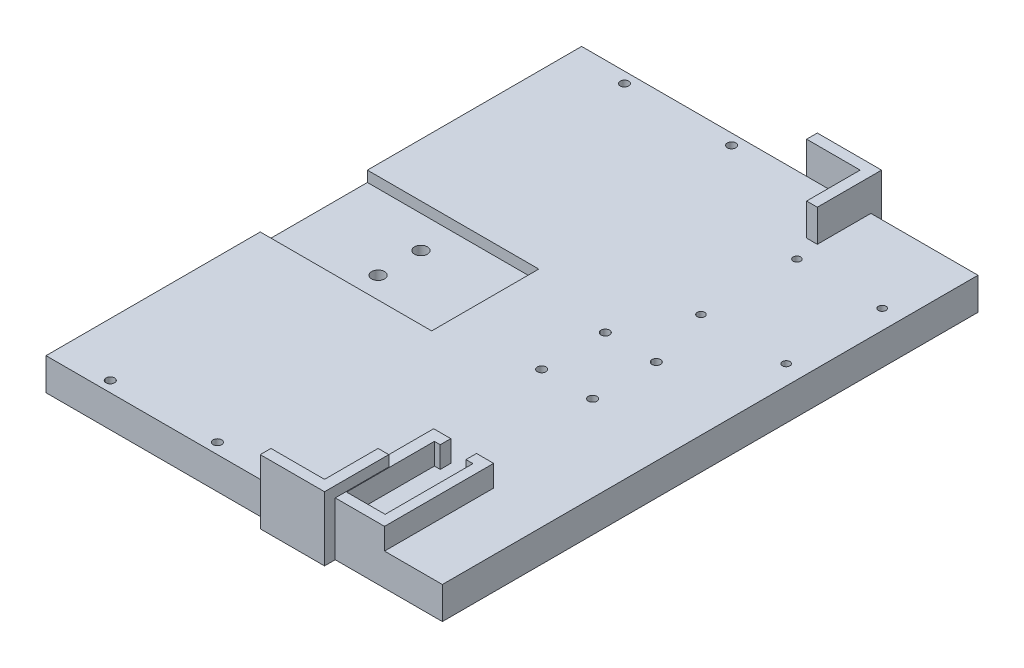
SolidWorks part; units mm, degrees
ref_plane "Ebene vorne" through (0, 0, 0) normal (0, 0, 1) x (1, 0, 0)
ref_plane "Ebene oben" through (0, 0, 0) normal (0, 1, 0) x (1, 0, 0)
ref_plane "Ebene rechts" through (0, 0, 0) normal (1, 0, 0) x (0, 0, -1)
sketch "Skizze1" plane through (0, 0, 0) normal (0, 1, 0) x (1, 0, 0)
  line L5 (-175, -125) -> (175, 125) construction
  line L6 (-175, 125) -> (175, -125) construction
  line L11 (-105, 125) -> (145, 125)
  line L12 (-105, -125) -> (-105, -65)
  line L13 (-105, 125) -> (-105, 65)
  line L14 (-105, -65) -> (-175, -65)
  line L15 (-105, 65) -> (-175, 65)
  line L17 (-105, -125) -> (145, -125)
  line L19 (185, 20) -> (145, 125)
  line L21 (175, 0) -> (175, 20)
  line L22 (175, 20) -> (185, 20)
  line L23 (185, 0) -> (185, 20)
  line L25 (185, 0) -> (185, -20)
  line L26 (185, -20) -> (175, -20)
  line L27 (175, 0) -> (175, -20)
  line L28 (185, -20) -> (145, -125)
  line L29 (-175, 65) -> (-175, -65)
  point P0 (0, 0)
  dimension "D1" = 350
  dimension "D2" = 250
  dimension "D3" = 60
  dimension "D4" = 250
  dimension "D5" = 40
  dimension "D6" = 130
  dimension "D7" = 70
  dimension "D8" = 20
  dimension "D9" = 10
extrude "Aufsatz-Linear austragen1" add sketch "Skizze1" along normal blind 15 contours L15 L29 L14 L12 L17 L28 L26 L27 L21 L22 L19 L11 L13 | L21 L27 L26 L25 L23 L22 region at (10.8182, 0, 0) region at (180, 0, 0)
sketch "Skizze2" plane through (0, 15, 0) normal (0, 1, 0) x (1, 0, 0)
  line L0 (-175, 65) -> (-175, -65) construction
  line L9 (-175, 62) -> (-110, 62)
  line L10 (-175, 62) -> (-175, 42)
  line L11 (-175, 42) -> (-110, 42)
  line L12 (-110, 62) -> (-110, 42)
  line L13 (-105, 65) -> (-175, 65) construction
  line L14 (-175, -42) -> (-110, -42)
  line L15 (-175, -42) -> (-175, -62)
  line L16 (-175, -62) -> (-110, -62)
  line L17 (-110, -42) -> (-110, -62)
  line L18 (-105, -65) -> (-175, -65) construction
  line L19 (-105, 125) -> (145, 125) construction
  line L24 (-125, -62) -> (-120, -62)
  line L25 (-125, -62) -> (-125, -65)
  line L26 (-125, -65) -> (-120, -65)
  line L27 (-120, -62) -> (-120, -65)
  line L28 (-125, -42) -> (-120, -42)
  line L29 (-125, -42) -> (-125, -38)
  line L30 (-125, -38) -> (-120, -38)
  line L31 (-120, -42) -> (-120, -38)
  line L32 (-125, 42) -> (-120, 42)
  line L33 (-125, 42) -> (-125, 38)
  line L34 (-125, 38) -> (-120, 38)
  line L35 (-120, 42) -> (-120, 38)
  line L36 (-125, 65) -> (-120, 65)
  line L37 (-125, 65) -> (-125, 62)
  line L38 (-125, 62) -> (-120, 62)
  line L39 (-120, 65) -> (-120, 62)
  line L40 (-105, -125) -> (145, -125)
  line L41 (-105, -125) -> (-105, 125)
  line L42 (-105, 125) -> (145, 125)
  line L43 (145, -125) -> (145, 125)
  line L46 (145, -125) -> (195, -125)
  line L47 (145, -125) -> (145, 125)
  line L48 (145, 125) -> (195, 125)
  line L49 (195, -125) -> (195, 125)
  line M8 (-105, 65) -> (-175, 65)
  dimension "D1" = 65
  dimension "D2" = 65
  dimension "D3" = 20
  dimension "D4" = 20
  dimension "D5" = 3
  dimension "D6" = 3
  dimension "D7" = 5
  dimension "D8" = 50
  dimension "D9" = 5
  dimension "D10" = 50
  dimension "D11" = 5
  dimension "D12" = 50
  dimension "D13" = 5
  dimension "D14" = 50
  dimension "D15" = 4
  dimension "D16" = 4
  dimension "D17" = 250
  dimension "D18" = 50
extrude "Aufsatz-Linear austragen2" add sketch "Skizze2" against normal blind 37 contours L14 L31 L30 L29 | L35 L11 L33 L34 | L39 L37 L9 M8 | L26 L27 L24 L25 region at (-122.5, 15, -63.5) region at (-122.5, 15, -40) region at (-122.5, 15, 40)
sketch "Skizze3" plane through (0, 15, 0) normal (0, 1, 0) x (1, 0, 0)
  line L0 (-105, 125) -> (145, 125) construction
  line L1 (-105, -125) -> (145, -125)
  line L2 (-105, -125) -> (-105, 125)
  line L3 (-105, 125) -> (145, 125)
  line L4 (145, -125) -> (145, 125)
  line L6 (145, -125) -> (195, -125)
  line L7 (145, -125) -> (145, 125)
  line L8 (145, 125) -> (195, 125)
  line L9 (195, -125) -> (195, 125)
  line M6 (145, -125) -> (185, -20)
  line M7 (185, -20) -> (185, 20)
  line M8 (185, 20) -> (145, 125)
  dimension "D1" = 250
  dimension "D2" = 50
extrude "Aufsatz-Linear austragen3" add sketch "Skizze3" against normal blind 15 contours L6 L9 L8 M8 M7 M6 region at (167.3825, 15, 73.4076)
sketch "Skizze4" plane through (0, 15, 0) normal (0, 1, 0) x (1, 0, 0)
  line L9 (195, -125) -> (200, -125)
  line L10 (195, -125) -> (195, 125)
  line L11 (195, 125) -> (200, 125)
  line L12 (200, -125) -> (200, 125)
  dimension "D3" = 250
  dimension "D4" = 5
extrude "Aufsatz-Linear austragen4" add sketch "Skizze4" against normal blind 15
sketch "Skizze5" plane through (0, 15, 0) normal (0, 1, 0) x (1, 0, 0)
  line L1 (-105, 125) -> (-75, 125)
  line L2 (-105, 125) -> (-105, 120)
  line L3 (-105, 120) -> (-75, 120)
  line L4 (-75, 125) -> (-75, 120)
  line L5 (-105, -125) -> (-75, -125)
  line L6 (-105, -125) -> (-105, -120)
  line L7 (-105, -120) -> (-75, -120)
  line L8 (-75, -125) -> (-75, -120)
  dimension "D1" = 30
  dimension "D2" = 30
  dimension "D3" = 5
  dimension "D4" = 5
extrude "Aufsatz-Linear austragen5" add sketch "Skizze5" against normal blind 30
sketch "Skizze6" plane through (0, 15, 0) normal (0, 1, 0) x (1, 0, 0)
  line L0 (-105, -125) -> (200, -125) construction
  line L1 (-110, -130) -> (-70.4119, -130)
  line L2 (-110, -130) -> (-110, -86.8064)
  line L3 (-110, -86.8064) -> (-70.4119, -86.8064)
  line L4 (-70.4119, -130) -> (-70.4119, -86.8064)
  line L5 (-110, 130) -> (-61.5934, 130)
  line L6 (-110, 130) -> (-110, 88.8696)
  line L7 (-110, 88.8696) -> (-61.5934, 88.8696)
  line L8 (-61.5934, 130) -> (-61.5934, 88.8696)
  line L9 (-105, -125) -> (-105, -65) construction
  line L10 (-105, 125) -> (-105, 65) construction
  line L11 (-105, 125) -> (200, 125) construction
  line L12 (-68.8744, -125) -> (-105, -125)
  line L13 (-105, -125) -> (-105, -86.8064)
  line L14 (-105, 84.0053) -> (-105, 125)
  line L15 (-105, 125) -> (-61.5934, 125)
  line M6 (-105, -65) -> (-105, -125)
  line M7 (-105, -125) -> (200, -125)
  line M9 (200, 125) -> (-105, 125)
  line M10 (-105, 125) -> (-105, 65)
  dimension "D1" = 5
  dimension "D2" = 5
  dimension "D3" = 5
  dimension "D4" = 5
extrude "Aufsatz-Linear austragen6" add sketch "Skizze6" along normal blind 15 separate body contours L8 L5 L6 L7 M10 M9 | L1 L4 L3 L2 M7 M6 region at (-109.4141, 15, 108.4032) region at (-85.7967, 15, -129.3648)
sketch "Skizze7" plane through (0, 0, 0) normal (0, -1, 0) x (1, 0, 0)
  line L7 (-110, -130) -> (-110, -88.8696)
  line L8 (-110, -88.8696) -> (-105, -88.8696)
  line L9 (-105, -130) -> (-105, -88.8696)
  line L10 (-110, 130) -> (-105, 130)
  line L11 (-110, 130) -> (-110, 86.8064)
  line L12 (-110, 86.8064) -> (-105, 86.8064)
  line L13 (-105, 130) -> (-105, 86.8064)
  line L14 (-110, 130) -> (-70.4119, 130)
  line L15 (-110, 130) -> (-110, 125)
  line L16 (-110, 125) -> (-70.4119, 125)
  line L17 (-70.4119, 130) -> (-70.4119, 125)
  line L18 (-110, -130) -> (-61.5934, -130)
  line L19 (-110, -130) -> (-110, -125)
  line L20 (-110, -125) -> (-61.5934, -125)
  line L21 (-61.5934, -130) -> (-61.5934, -125)
  line M7 (-105, 120) -> (-105, 65)
  line M19 (-105, -65) -> (-105, -120)
  line M22 (-75, -125) -> (200, -125)
  line M24 (200, 125) -> (-75, 125)
extrude "Aufsatz-Linear austragen7" add sketch "Skizze7" against normal blind 15 contours L7 L20 L9 L8 M19 | L20 L7 L18 L9 | L18 L21 L20 L9 M22 | L16 L11 L12 L13 M7 | L11 L16 L13 L10 | L17 L14 L13 L16 M24 region at (-107.5, 0, -127.5) region at (-107.5, 0, -106.9348) region at (-83.2967, 0, -127.5) region at (-107.5, 0, 127.5) region at (-87.7059, 0, 127.5) region at (-107.5, 0, 105.9032)
sketch "Skizze8" plane through (0, 15, 0) normal (0, 1, 0) x (1, 0, 0)
  line L0 (-61.5934, 125) -> (200, 125) construction
  line L1 (-105, -125) -> (145, -125)
  line L2 (-105, -125) -> (-105, 125)
  line L3 (-105, 125) -> (145, 125)
  line L4 (145, -125) -> (145, 125)
  line L6 (150, -130) -> (109.2888, -130)
  line L7 (150, -130) -> (150, -94.2536)
  line L8 (150, -94.2536) -> (109.2888, -94.2536)
  line L9 (109.2888, -130) -> (109.2888, -94.2536)
  line L10 (150, 130) -> (118.9946, 130)
  line L11 (150, 130) -> (150, 95.9912)
  line L12 (150, 95.9912) -> (118.9946, 95.9912)
  line L13 (118.9946, 130) -> (118.9946, 95.9912)
  line M9 (-70.4119, -125) -> (200, -125)
  line M11 (200, 125) -> (-61.5934, 125)
  dimension "D1" = 250
  dimension "D2" = 5
  dimension "D3" = 5
  dimension "D4" = 5
  dimension "D5" = 5
extrude "Aufsatz-Linear austragen8" add sketch "Skizze8" along normal blind 15 and the other way blind 15 contours L7 L8 L4 M9 | L9 L6 L7 L1 M9 | L12 L11 L4 M11 | L10 L13 L11 M11 region at (129.6444, 15, 127.5) region at (147.5, 15, 109.6268) region at (134.4973, 15, -127.5) region at (147.5, 15, -110.4956)
sketch "Skizze9" plane through (0, 15, 0) normal (0, 1, 0) x (1, 0, 0)
  line L1 (150, -125) -> (200, -125)
  line L2 (150, -125) -> (150, 125)
  line L3 (150, 125) -> (200, 125)
  line L4 (200, -125) -> (200, 125)
  line L5 (150, 9) -> (196, 9)
  line L6 (150, 9) -> (150, 120)
  line L7 (150, 120) -> (196, 120)
  line L8 (196, 9) -> (196, 120)
  line L10 (200, 105) -> (196, 105)
  line L12 (155, 4) -> (145, 4)
  line L13 (155, 4) -> (155, 14)
  line L14 (155, 14) -> (145, 14)
  line L15 (145, 4) -> (145, 14)
  line L17 (190, 14) -> (200, 14)
  line L18 (190, 14) -> (190, 4)
  line L19 (190, 4) -> (200, 4)
  line L20 (200, 14) -> (200, 4)
  line M10 (150, 125) -> (150, 95.9912)
  line M31 (200, 125) -> (150, 125)
  dimension "D1" = 46
  dimension "D2" = 111
  dimension "D3" = 5
  dimension "D4" = 20
  dimension "D5" = 10
  dimension "D6" = 10
  dimension "D7" = 5
  dimension "D8" = 5
  dimension "D9" = 10
  dimension "D10" = 10
  dimension "D11" = 5
extrude "Aufsatz-Linear austragen10" add sketch "Skizze9" along normal blind 15 contours L15 L12 L2 L14 | L12 L13 L5 L2 | L18 L19 L4 L17 L8 L5 | L10 L4 L7 L8 M31 M10 region at (147.5, 15, -9) region at (152.5, 15, -6.5) region at (195.8571, 15, -7.9286) region at (179.4516, 15, -120.5645)
sketch "Skizze10" plane through (118.9946, 0, 0) normal (-1, 0, 0) x (0, 0, 1)
  line L1 (-125, 30) -> (-130, 30)
  line L2 (-125, 30) -> (-125, 0)
  line L3 (-125, 0) -> (-130, 0)
  line L4 (-130, 30) -> (-130, 0)
extrude "Schnitt-Linear austragen1" cut sketch "Skizze10" against normal blind 1.01
sketch "Skizze12" plane through (0, 15, 0) normal (0, 1, 0) x (1, 0, 0)
  line L0 (-105, 125) -> (-105, 88.8696) construction
  line L1 (-110, 130) -> (-105, 130)
  line L2 (-110, 130) -> (-110, 100)
  line L3 (-110, 100) -> (-105, 100)
  line L4 (-105, 130) -> (-105, 100)
  line L5 (145, 95.9912) -> (145, 125) construction
  line L6 (-105, -125) -> (-70.4119, -125) construction
  line L7 (-110, -130) -> (-80, -130)
  line L8 (-110, -130) -> (-110, -125)
  line L9 (-110, -125) -> (-80, -125)
  line L10 (-80, -130) -> (-80, -125)
  line L11 (-61.5934, 125) -> (-105, 125) construction
  line L12 (-110, 130) -> (-80, 130)
  line L13 (-110, 130) -> (-110, 125)
  line L14 (-110, 125) -> (-80, 125)
  line L15 (-80, 130) -> (-80, 125)
  line L16 (120.0046, 125) -> (145, 125) construction
  line L17 (150, 130) -> (120, 130)
  line L18 (150, 130) -> (150, 125)
  line L19 (150, 125) -> (120, 125)
  line L20 (120, 130) -> (120, 125)
  line L21 (150, 130) -> (145, 130)
  line L22 (150, 130) -> (150, 100)
  line L23 (150, 100) -> (145, 100)
  line L24 (145, 130) -> (145, 100)
  line L25 (145, -125) -> (145, -94.2536) construction
  line L26 (150, -130) -> (145, -130)
  line L27 (150, -130) -> (150, -100)
  line L28 (150, -100) -> (145, -100)
  line L29 (145, -130) -> (145, -100)
  line L30 (109.2888, -125) -> (145, -125) construction
  line L31 (150, -130) -> (120, -130)
  line L32 (150, -130) -> (150, -125)
  line L33 (150, -125) -> (120, -125)
  line L34 (120, -130) -> (120, -125)
  line L36 (-105, -86.8064) -> (-105, -125) construction
  line L37 (-110, -130) -> (-105, -130)
  line L38 (-110, -130) -> (-110, -100)
  line L39 (-110, -100) -> (-105, -100)
  line L40 (-105, -130) -> (-105, -100)
  line L42 (-80, -125) -> (-70.4119, -125)
  line L43 (-80, -125) -> (-80, -130)
  line L44 (-80, -130) -> (-70.4119, -130)
  line L45 (-70.4119, -125) -> (-70.4119, -130)
  line L46 (-105, -100) -> (-110, -100)
  line L47 (-105, -100) -> (-105, -86.8064)
  line L48 (-105, -86.8064) -> (-110, -86.8064)
  line L49 (-110, -100) -> (-110, -86.8064)
  line L50 (-105, 100) -> (-110, 100)
  line L51 (-105, 100) -> (-105, 88.8696)
  line L52 (-105, 88.8696) -> (-110, 88.8696)
  line L53 (-110, 100) -> (-110, 88.8696)
  line L54 (-80, 125) -> (-61.5934, 125)
  line L55 (-80, 125) -> (-80, 130)
  line L56 (-80, 130) -> (-61.5934, 130)
  line L57 (-61.5934, 125) -> (-61.5934, 130)
  line L58 (150, 100) -> (145, 100)
  line L59 (150, 100) -> (150, 95.9912)
  line L60 (150, 95.9912) -> (145, 95.9912)
  line L61 (145, 100) -> (145, 95.9912)
  line L62 (150, -100) -> (145, -100)
  line L63 (150, -100) -> (150, -94.2536)
  line L64 (150, -94.2536) -> (145, -94.2536)
  line L65 (145, -100) -> (145, -94.2536)
  line L66 (120, -125) -> (109.2888, -125)
  line L67 (120, -125) -> (120, -130)
  line L68 (120, -130) -> (109.2888, -130)
  line L69 (109.2888, -125) -> (109.2888, -130)
  line M12 (150, 120) -> (150, 95.9912)
  line M13 (150, 95.9912) -> (145, 95.9912)
  line M14 (145, 95.9912) -> (145, 125)
  line M17 (-61.5934, 125) -> (-105, 125)
  line M18 (-105, 125) -> (-105, 88.8696)
  line M24 (-105, -86.8064) -> (-105, -125)
  line M25 (-105, -125) -> (-70.4119, -125)
  line M27 (109.2888, -125) -> (145, -125)
  line M28 (145, -125) -> (145, -94.2536)
  line M29 (145, -94.2536) -> (150, -94.2536)
  line M30 (150, -94.2536) -> (150, -125)
  dimension "D1" = 30
  dimension "D2" = 30
  dimension "D3" = 30
  dimension "D4" = 30
  dimension "D5" = 30
  dimension "D6" = 30
  dimension "D7" = 30
  dimension "D8" = 30
extrude "Schnitt-Linear austragen2" cut sketch "Skizze12" along normal blind 15 contours L69 L68 L34 M27 | L28 M30 M29 M28 | L23 M12 M14 M13 | L57 L56 L15 M17 | L3 L53 L52 M18 | L45 L10 L44 M25 | L49 L39 L48 M24 region at (-70.7967, 15, -127.5) region at (-107.5, 15, -94.4348) region at (-75.2059, 15, 127.5) region at (-107.5, 15, 93.4032) region at (147.5, 15, -97.9956) region at (114.6444, 15, 127.5) region at (147.5, 15, 97.1268)
sketch "Skizze13" plane through (0, 15, 0) normal (0, 1, 0) x (1, 0, 0)
  line L1 (109.2888, -130) -> (120, -130)
  line L2 (109.2888, -130) -> (109.2888, -125)
  line L3 (109.2888, -125) -> (120, -125)
  line L4 (120, -130) -> (120, -125)
  line L5 (-70.4119, -130) -> (-80, -130)
  line L6 (-70.4119, -130) -> (-70.4119, -125)
  line L7 (-70.4119, -125) -> (-80, -125)
  line L8 (-80, -130) -> (-80, -125)
  line L9 (-110, -86.8064) -> (-105, -86.8064)
  line L10 (-110, -86.8064) -> (-110, -100)
  line L11 (-110, -100) -> (-105, -100)
  line L12 (-105, -86.8064) -> (-105, -100)
  line L13 (-110, 88.8696) -> (-105, 88.8696)
  line L14 (-110, 88.8696) -> (-110, 100)
  line L15 (-110, 100) -> (-105, 100)
  line L16 (-105, 88.8696) -> (-105, 100)
  line L17 (-61.5934, 130) -> (-80, 130)
  line L18 (-61.5934, 130) -> (-61.5934, 125)
  line L19 (-61.5934, 125) -> (-80, 125)
  line L20 (-80, 130) -> (-80, 125)
extrude "Schnitt-Linear austragen3" cut sketch "Skizze13" against normal blind 15
sketch "Skizze14" plane through (0, 15, 0) normal (0, 1, 0) x (1, 0, 0)
  line L1 (-175, -65) -> (-105, -65)
  line L2 (-175, -65) -> (-175, 65)
  line L3 (-175, 65) -> (-105, 65)
  line L4 (-105, -65) -> (-105, 65)
  line L5 (-175, -25) -> (-105, -25)
  line L6 (-175, -25) -> (-175, 25)
  line L7 (-175, 25) -> (-105, 25)
  line L8 (-105, -25) -> (-105, 25)
  line L9 (-105, -25) -> (-125, -25)
  line L10 (-105, -25) -> (-105, 25)
  line L11 (-105, 25) -> (-125, 25)
  line L12 (-125, -25) -> (-125, 25)
  line M34 (-105, 65) -> (-175, 65)
  line M35 (-175, 65) -> (-175, -65)
  line M36 (-175, -65) -> (-105, -65)
  dimension "D1" = 50
  dimension "D2" = 40
  dimension "D3" = 20
  dimension "D4" = 50
extrude "Aufsatz-Linear austragen11" add sketch "Skizze14" along normal blind 20 contours L5 L2 L4 M36 | L5 L12 L7 L2 | L12 L5 L4 L7 | L7 L4 M35 M34 region at (-140, 15, 45) region at (-150, 15, 0) region at (-115, 15, 0) region at (-140, 15, -45)
chamfer "Fase2" distance 20 distance2 50 1 edges at (-175, 35, 0) first distance on face at (-175, 17.5, 0)
chamfer "Fase3" distance 20 distance2 35 2 edges at (-115, 35, -65) (-115, 35, 65) first distance on face at (-128, 5.6, -65) first distance on face at (-128, 5.6, 65)
chamfer "Fase4" distance 20 distance2 20 2 edges at (-150, 25, 47.5) (-150, 25, -47.5)
sketch "Skizze15" plane through (-11.552, 55.8863, -15.4322) normal (-0.1954, 0.9453, -0.261) x (0.9807, 0.1884, -0.052)
  line L0 (-95.2849, 28.8709) -> (-95.2849, 11.0403) construction
  line L1 (-115.678, -3.3909) -> (-166.6609, 35.67) construction
  circle A0 centre (-117.2849, 20.601) radius 10
  circle A1 centre (-142.8398, 36.3157) radius 7.5
  dimension "D1" = 20
  dimension "D2" = 15
  dimension "D3" = 30
  dimension "D4" = 22
  dimension "D5" = 15
extrude "Aufsatz-Linear austragen12" add sketch "Skizze15" along normal blind 3
fillet "Verrundung1" radius 10 2 edges at (-152.2243, 24.1474, -36.5621) (-127.1621, 33.8091, -20.3337)
sketch "Skizze18" plane through (-11.552, 55.8863, 15.4322) normal (-0.1954, 0.9453, 0.261) x (0.9807, 0.1884, 0.052)
  line L0 (-166.6609, -35.67) -> (-115.678, 3.3909) construction
  line L1 (-95.2849, -11.0403) -> (-95.2849, -28.8709) construction
  circle A0 centre (-117.2849, -25.9789) radius 10
  circle A1 centre (-147.2849, -39.7214) radius 7.5
  dimension "D1" = 20
  dimension "D2" = 15
  dimension "D3" = 30
  dimension "D4" = 15
  dimension "D5" = 22
extrude "Aufsatz-Linear austragen13" add sketch "Skizze18" along normal blind 3
fillet "Verrundung2" radius 10 2 edges at (-156.5838, 18.411, 54.0726) (-127.1621, 27.0541, 44.7961)
sketch "Skizze19" plane through (-29.3103, 73.2759, 0) normal (-0.3714, 0.9285, 0) x (0.9285, 0.3714, 0)
  line L0 (-156.9126, -41.147) -> (-156.9126, 41.147) construction
  line L1 (-103.0609, 6.147) -> (-103.0609, -6.147) construction
  line L3 (-156.9126, -41.147) -> (-103.0609, -6.147) construction
  line L4 (-103.0609, 6.147) -> (-156.9126, 41.147) construction
  circle A0 centre (-118.0609, -0.0632) radius 10
  circle A1 centre (-139.8608, 12.1747) radius 10
  circle A2 centre (-139.9126, -12.2084) radius 10
  dimension "D1" = 15
  dimension "D2" = 15
  dimension "D3" = 17
  dimension "D4" = 17.0518
  dimension "D5" = 25
  dimension "D7" = 15
  dimension "D8" = 25
extrude "Aufsatz-Linear austragen14" add sketch "Skizze19" along normal blind 3
fillet "Verrundung3" radius 10 3 edges at (-149.3261, 28.5007, 0.0632) (-169.6148, 20.3852, 12.2084) (-169.5667, 20.4044, -12.1747)
sketch "Skizze20" plane through (0, 0, -65) normal (0, 0, -1) x (-1, 0, 0)
  line L1 (120, -22) -> (125, -22) construction
  line L2 (120, 0) -> (125, 0)
  line L3 (120, -22) -> (120, 0) construction
  line L4 (125, -22) -> (125, 0) construction
  circle A0 centre (122.5, -19.5) radius 1.5
  circle A1 centre (122.5, -2.5) radius 1.5
  dimension "D1" = 3
  dimension "D2" = 3
  dimension "D3" = 2.5
  dimension "D4" = 2.5
  dimension "D5" = 2.5
  dimension "D6" = 2.5
extrude "Schnitt-Linear austragen4" cut sketch "Skizze20" against normal blind 250 contours A0 | A1 region at (-122.5, -19.5, -65) region at (-122.5, -2.5, -65)
sketch "Skizze21" plane through (0, 15, 0) normal (0, 1, 0) x (1, 0, 0)
  line L0 (200, -125) -> (200, 4) construction
  line L1 (197.5893, -53.9558) -> (147.5893, -53.9558)
  line L2 (197.5893, -53.9558) -> (197.5893, 1.0442)
  line L3 (197.5893, 1.0442) -> (147.5893, 1.0442)
  line L4 (147.5893, -53.9558) -> (147.5893, 1.0442)
  line L9 (150, -100) -> (191, -100)
  line L10 (150, -100) -> (150, -118)
  line L11 (150, -118) -> (191, -118)
  line L12 (191, -100) -> (191, -118)
  line L13 (145, -100) -> (195, -100)
  line L14 (145, -100) -> (145, -93)
  line L15 (145, -93) -> (195, -93)
  line L16 (195, -100) -> (195, -93)
  line L17 (150, -125) -> (200, -125)
  line L18 (150, -125) -> (150, -118)
  line L19 (150, -118) -> (200, -118)
  line L20 (200, -125) -> (200, -118)
  line L22 (195, -93) -> (191, -93)
  line L23 (195, -93) -> (195, -105.2)
  line L24 (195, -105.2) -> (191, -105.2)
  line L25 (191, -93) -> (191, -105.2)
  line L26 (195, -125) -> (191, -125)
  line L27 (195, -125) -> (195, -112.8)
  line L28 (195, -112.8) -> (191, -112.8)
  line L29 (191, -125) -> (191, -112.8)
  line M31 (145, -100) -> (150, -100)
  line M32 (150, -100) -> (150, -125)
  line M33 (150, -125) -> (200, -125)
  dimension "D1" = 55
  dimension "D2" = 50
  dimension "D3" = 41
  dimension "D4" = 18
  dimension "D5" = 7
  dimension "D6" = 4
  dimension "D7" = 12.2
  dimension "D8" = 4
  dimension "D9" = 12.2
extrude "Aufsatz-Linear austragen15" add sketch "Skizze21" along normal blind 10 contours L25 L15 L14 L9 M31 | L15 L25 L13 L16 | L24 L23 L13 L12 | L29 L11 M33 M32 | L29 L17 L27 L19 | L27 L28 L12 L19 region at (168, 15, 96.5) region at (193, 15, 102.6) region at (193, 15, 96.5) region at (170.5, 15, 121.5) region at (193, 15, 115.4) region at (193, 15, 121.5)
sketch "Skizze22" plane through (0, 15, 0) normal (0, 1, 0) x (1, 0, 0)
  line L1 (140.9695, -63.333) -> (190.9695, -63.333)
  line L2 (140.9695, -63.333) -> (140.9695, -8.333)
  line L3 (140.9695, -8.333) -> (190.9695, -8.333)
  line L4 (190.9695, -63.333) -> (190.9695, -8.333)
  circle A0 centre (146.0695, -58.233) radius 1.75
  circle A1 centre (146.0695, -13.433) radius 1.75
  circle A2 centre (185.8695, -58.233) radius 1.75
  circle A3 centre (185.8695, -13.433) radius 1.75
  dimension "D1" = 3.5
  dimension "D2" = 3.5
  dimension "D3" = 3.5
  dimension "D4" = 3.5
  dimension "D5" = 5.1
  dimension "D6" = 5.1
  dimension "D7" = 50
  dimension "D8" = 55
  dimension "D9" = 5.1
  dimension "D10" = 5.1
  dimension "D11" = 5.1
  dimension "D12" = 5.1
  dimension "D13" = 5.1
  dimension "D14" = 5.1
extrude "Schnitt-Linear austragen5" cut sketch "Skizze22" against normal blind 20 contours A0 | A1 | A3 | A2
sketch "Skizze23" plane through (0, 15, 0) normal (0, 1, 0) x (1, 0, 0)
  line L0 (200, 14) -> (200, 105) construction
  line L1 (-175, 149.5923) -> (15, 149.5923)
  line L2 (-175, 149.5923) -> (-175, -153.0489)
  line L3 (-175, -153.0489) -> (15, -153.0489)
  line L4 (15, 149.5923) -> (15, -153.0489)
  dimension "D1" = 190
  dimension "D2" = 185
extrude "Schnitt-Linear austragen6" cut sketch "Skizze23" against normal blind 47 and the other way blind 59 contours L2 L1 L4 L3
sketch "Skizze24" plane through (15, 0, 0) normal (-1, 0, 0) x (0, 0, 1)
  line L0 (125, 15) -> (-125, 15) construction
  line L1 (-25, 15) -> (25, 15)
  line L2 (-25, 15) -> (-25, 10)
  line L3 (-25, 10) -> (25, 10)
  line L4 (25, 15) -> (25, 10)
  line L5 (-125, 0) -> (-125, 15) construction
  dimension "D1" = 50
  dimension "D2" = 5
  dimension "D3" = 100
extrude "Schnitt-Linear austragen7" cut sketch "Skizze24" against normal blind 80
sketch "Skizze25" plane through (0, 10, 0) normal (0, 1, 0) x (1, 0, 0)
  line L0 (95, -25) -> (95, 25) construction
  line L1 (95, -25) -> (15, -25) construction
  circle A0 centre (65, 0) radius 12.5
  dimension "D1" = 25
  dimension "D2" = 30
  dimension "D3" = 25
extrude "Schnitt-Linear austragen8" cut sketch "Skizze25" against normal blind 80
sketch "Skizze26" plane through (0, 0, 0) normal (0, -1, 0) x (1, 0, 0)
  circle A0 centre (65, 0) radius 17.5909
extrude "Aufsatz-Linear austragen16" add sketch "Skizze26" against normal blind 10
sketch "Skizze27" plane through (0, 15, 0) normal (0, 1, 0) x (1, 0, 0)
  line L5 (95, 25) -> (15, 25)
  line L6 (95, 25) -> (95, -25)
  line L7 (95, -25) -> (15, -25)
  line L8 (15, 25) -> (15, -25)
  circle A0 centre (75, 10) radius 3
  circle A1 centre (75, -10) radius 3
  circle A2 centre (35, 10) radius 3
  circle A3 centre (35, -10) radius 3
  dimension "D7" = 6
  dimension "D8" = 6
  dimension "D11" = 6
  dimension "D12" = 6
  dimension "D1" = 40
  dimension "D2" = 20
  dimension "D3" = 20
  dimension "D4" = 40
  dimension "D5" = 20
  dimension "D6" = 15
  dimension "D9" = 20
  dimension "D10" = 15
extrude "Schnitt-Linear austragen10" cut sketch "Skizze27" against normal blind 93 contours A0 | A1 | A2 | A3
sketch "Skizze28" plane through (0, 15, 0) normal (0, 1, 0) x (1, 0, 0)
  line L0 (95, 25) -> (95, 0)
  line L5 (95, -25) -> (95, 25) construction
  line L6 (95, 0) -> (200, 0)
  line L7 (200, -125) -> (200, 4) construction
  line L8 (200, 14) -> (200, 105) construction
  circle A0 centre (160, -14.85) radius 2
  circle A1 centre (160, 14.85) radius 2
  circle A2 centre (136.2, 14.85) radius 2
  circle A3 centre (136.2, -14.85) radius 2
  dimension "D3" = 4
  dimension "D4" = 4
  dimension "D5" = 4
  dimension "D6" = 4
  dimension "D1" = 29.7
  dimension "D2" = 29.7
  dimension "D7" = 23.8
  dimension "D8" = 23.8
  dimension "D9" = 14.85
  dimension "D10" = 14.85
  dimension "D11" = 40
  dimension "D12" = 40
extrude "Schnitt-Linear austragen11" cut sketch "Skizze28" against normal blind 93 contours A1 | A0 | A3 | A2 region at (160, 15, 14.85) region at (160, 15, -14.85) region at (136.2, 15, -14.85) region at (136.2, 15, 14.85)
sketch "Skizze29" plane through (0, 15, 0) normal (0, 1, 0) x (1, 0, 0)
  line L1 (145, 125) -> (15, 125)
  line L2 (15, 25) -> (15, 125) construction
  line L3 (15, -125) -> (15, -25) construction
  line L4 (15, -125) -> (120, -125) construction
  circle A0 centre (90, 120) radius 2
  circle A1 centre (40, 120) radius 2
  circle A2 centre (90, -120) radius 2
  circle A3 centre (40, -120) radius 2
  dimension "D1" = 4
  dimension "D2" = 4
  dimension "D3" = 4
  dimension "D4" = 4
  dimension "D5" = 50
  dimension "D6" = 25
  dimension "D7" = 5
  dimension "D8" = 5
  dimension "D9" = 50
  dimension "D10" = 25
  dimension "D11" = 5
extrude "Schnitt-Linear austragen13" cut sketch "Skizze29" against normal blind 20 contours A0 | A1 | A2 | A3 region at (90, 15, -120) region at (40, 15, -120) region at (90, 15, 120) region at (40, 15, 120)
sketch "Skizze30" plane through (0, 10, 0) normal (0, 1, 0) x (1, 0, 0)
  line L1 (95, 25) -> (15, 25)
  line L2 (95, 25) -> (95, -25)
  line L3 (95, -25) -> (15, -25)
  line L4 (15, 25) -> (15, -25)
extrude "Aufsatz-Linear austragen17" add sketch "Skizze30" against normal blind 7
sketch "Skizze31" plane through (0, 10, 0) normal (0, 1, 0) x (1, 0, 0)
  line L0 (95, 25) -> (15, 25) construction
  line L1 (95, -25) -> (95, 25) construction
  circle A0 centre (55, 10) radius 3
  circle A1 centre (55, -10) radius 3
  dimension "D1" = 6
  dimension "D2" = 6
  dimension "D3" = 20
  dimension "D4" = 15
  dimension "D5" = 40
extrude "Schnitt-Linear austragen14" cut sketch "Skizze31" against normal blind 27
sketch "Skizze32" plane through (0, 0, 0) normal (0, -1, 0) x (1, 0, 0)
  circle A0 centre (75, -10) radius 3
  circle A1 centre (75, 10) radius 3.7236
  circle A2 centre (35, 10) radius 5.2534
  circle A3 centre (35, -10) radius 5.5871
extrude "Aufsatz-Linear austragen18" add sketch "Skizze32" against normal blind 9
sketch "Skizze35" plane through (0, 15, 0) normal (0, 1, 0) x (1, 0, 0)
  line L1 (197.0348, -115.503) -> (233.2763, -115.503)
  line L2 (197.0348, -115.503) -> (197.0348, -91.503)
  line L3 (197.0348, -91.503) -> (233.2763, -91.503)
  line L4 (233.2763, -115.503) -> (233.2763, -91.503)
  circle A0 centre (146.0695, -58.233) radius 1.75
  circle A1 centre (146.0695, -13.433) radius 1.75
  circle A2 centre (185.8695, -13.433) radius 1.75
  circle A3 centre (185.8695, -58.233) radius 1.75
  circle A4 centre (151.2105, 44.4776) radius 1.75
  circle A5 centre (191.0105, 44.4785) radius 1.75
  circle A6 centre (151.2105, 89.2776) radius 1.75
  circle A7 centre (191.0105, 89.2785) radius 1.75
  point P24 (193.2093, 43.8167)
  point P25 (154.9514, 48.5631)
  point P26 (154.3345, 42.8915)
  point P27 (193.2093, 40.4241)
  point P28 (151.2105, 88.6042)
  point P29 (151.2105, 44.4776)
  point P30 (191.0105, 44.4776)
  point P31 (0, 0)
  dimension "D4" = 3.5
  dimension "D5" = 3.5
  dimension "D6" = 3.5
  dimension "D7" = 3.5
  dimension "D1" = 24
  dimension "D2" = 44.8
  dimension "D3" = 39.8
  dimension "D8" = 39.8
  dimension "D9" = 44.8
  dimension "D10" = 39.8
  dimension "D11" = 44.8
extrude "Schnitt-Linear austragen16" cut sketch "Skizze35" against normal blind 20 contours A4 | A6 | A5 | A7
sketch "Skizze36" plane through (0, 15, 0) normal (0, 1, 0) x (1, 0, 0)
  circle A0 centre (146.0971, -61.909) radius 6.8466
  circle A1 centre (186.6852, -57.9261) radius 4.4713
  circle A2 centre (186.6852, -12.786) radius 4.8942
  circle A3 centre (146.0971, -12.786) radius 3.5251
extrude "Aufsatz-Linear austragen19" add sketch "Skizze36" against normal blind 15
sketch "Skizze39" plane through (0, 15, 0) normal (0, 1, 0) x (1, 0, 0)
  line L1 (200, -125) -> (150, -125)
  line L2 (200, -125) -> (200, 125)
  line L3 (200, 125) -> (150, 125)
  line L4 (150, -125) -> (150, 125)
extrude "Schnitt-Linear austragen17" cut sketch "Skizze39" along normal blind 57
sketch "Skizze40" plane through (0, 15, 0) normal (0, 1, 0) x (1, 0, 0)
  line L1 (154.2583, 18.1172) -> (142.8019, 18.1172)
  line L2 (154.2583, 18.1172) -> (154.2583, -99.7777)
  line L3 (154.2583, -99.7777) -> (142.8019, -99.7777)
  line L4 (142.8019, 18.1172) -> (142.8019, -99.7777)
extrude "Schnitt-Linear austragen18" cut sketch "Skizze40" along normal blind 86
sketch "Skizze41" plane through (0, 15, 0) normal (0, 1, 0) x (1, 0, 0)
  line L1 (150.3591, -99.2895) -> (145, -99.2895)
  line L2 (150.3591, -99.2895) -> (150.3591, -100)
  line L3 (150.3591, -100) -> (145, -100)
  line L4 (145, -99.2895) -> (145, -100)
extrude "Schnitt-Linear austragen19" cut sketch "Skizze41" along normal blind 69
sketch "Skizze42" plane through (0, 15, 0) normal (0, 1, 0) x (1, 0, 0)
  line L1 (150.2826, -120) -> (168.2826, -120)
  line L2 (150.2826, -120) -> (150.2826, -79)
  line L3 (150.2826, -79) -> (168.2826, -79)
  line L4 (168.2826, -120) -> (168.2826, -79)
  line L5 (145, -125) -> (173, -125)
  line L6 (145, -125) -> (145, -74.0666)
  line L7 (145, -74.0666) -> (173, -74.0666)
  line L8 (173, -125) -> (173, -74.0666)
  line L9 (153, -74.0666) -> (165, -74.0666)
  line L10 (153, -74.0666) -> (153, -79)
  line L11 (153, -79) -> (165, -79)
  line L12 (165, -74.0666) -> (165, -79)
  point P12 (145, -125)
  point P14 (145, -125)
  point P15 (145, -125)
  point P16 (145, -125)
  point P17 (0, 0)
  point P18 (145, -125)
  line M14 (145, -100) -> (150, -100)
  line M15 (150, -100) -> (150, -125)
  line M16 (150, -125) -> (200, -125)
  dimension "D1" = 18
  dimension "D2" = 41
  dimension "D3" = 12
  dimension "D4" = 8
  dimension "D5" = 8
  dimension "D6" = 5
extrude "Aufsatz-Linear austragen20" add sketch "Skizze42" along normal blind 10 contours L7 L12 L3 L4 L1 L2 L10 L6 L8 M14 M15 M16 region at (159.2826, 15, 120.5812)
